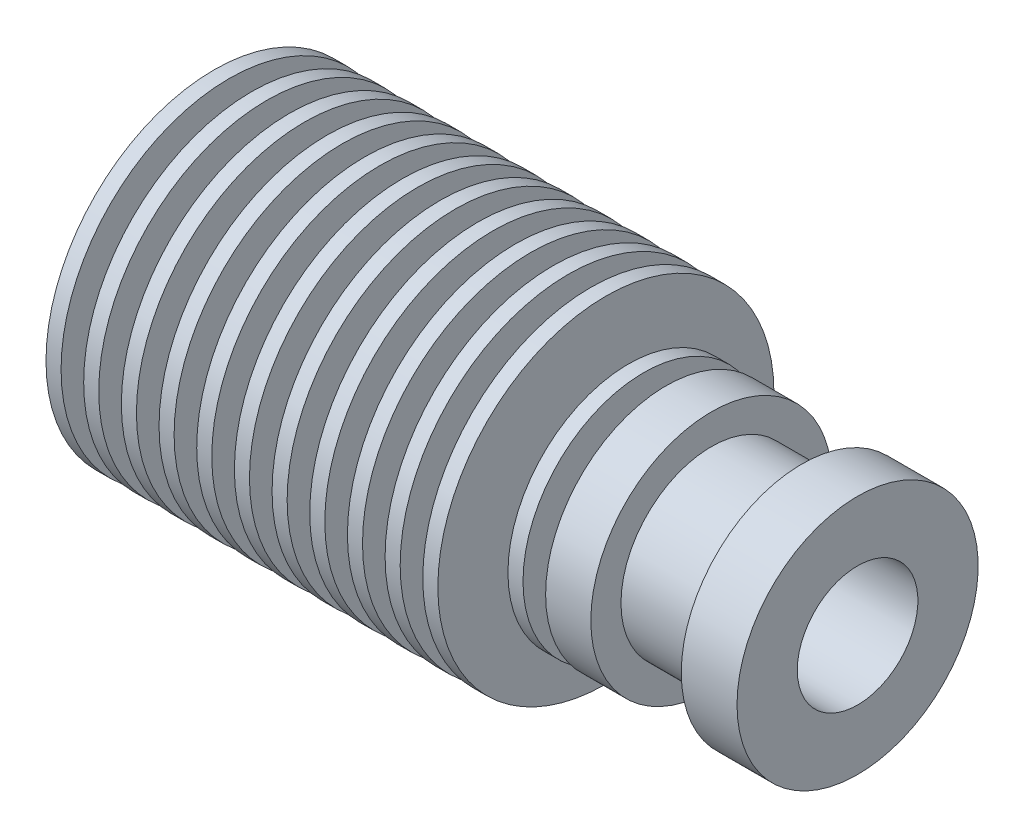
SolidWorks part; units mm, degrees
material "1060 Alloy"
ref_plane "Front Plane" through (0, 0, 0) normal (0, 0, 1) x (1, 0, 0)
ref_plane "Top Plane" through (0, 0, 0) normal (0, 1, 0) x (1, 0, 0)
ref_plane "Right Plane" through (0, 0, 0) normal (1, 0, 0) x (0, 0, -1)
sketch "Sketch1" plane through (0, 0, 0) normal (0, 0, 1) x (1, 0, 0)
  line L5 (9.7, 11.5342) -> (6, 11.5342)
  line L6 (6, 11.5342) -> (6, 13.5342)
  line L7 (6, 13.5342) -> (0, 13.5342)
  line L8 (0, 13.5342) -> (0, 11.5342)
  line L9 (0, 11.5342) -> (-3, 11.5342)
  line L10 (-3, 11.5342) -> (-3, 15.5342)
  line L12 (-32, 14.0576) -> (-30.5, 14.134)
  line L13 (-33, 14.0142) -> (-33, 8.3842)
  line L14 (-33, 8.3842) -> (-32, 8.3842)
  line L15 (-32, 8.3842) -> (-32, 14.0576)
  line L16 (-29.5, 8.3842) -> (-29.5, 14.1849)
  line L17 (-30.5, 14.134) -> (-30.5, 8.3842)
  line L18 (-30.5, 8.3842) -> (-29.5, 8.3842)
  line L19 (-27, 8.3842) -> (-27, 14.3122)
  line L20 (-28, 14.2613) -> (-28, 8.3842)
  line L21 (-28, 8.3842) -> (-27, 8.3842)
  line L22 (-24.5, 8.3842) -> (-24.5, 14.4395)
  line L23 (-25.5, 14.3886) -> (-25.5, 8.3842)
  line L24 (-25.5, 8.3842) -> (-24.5, 8.3842)
  line L25 (-22, 8.3842) -> (-22, 14.5668)
  line L26 (-23, 14.5159) -> (-23, 8.3842)
  line L27 (-23, 8.3842) -> (-22, 8.3842)
  line L28 (-19.5, 8.3842) -> (-19.5, 14.6941)
  line L29 (-20.5, 14.6432) -> (-20.5, 8.3842)
  line L30 (-20.5, 8.3842) -> (-19.5, 8.3842)
  line L31 (-17, 8.3842) -> (-17, 14.8214)
  line L32 (-18, 14.7705) -> (-18, 8.3842)
  line L33 (-18, 8.3842) -> (-17, 8.3842)
  line L34 (-14.5, 8.3842) -> (-14.5, 14.9487)
  line L35 (-15.5, 14.8977) -> (-15.5, 8.3842)
  line L36 (-15.5, 8.3842) -> (-14.5, 8.3842)
  line L37 (-12, 8.3842) -> (-12, 15.076)
  line L38 (-13, 15.025) -> (-13, 8.3842)
  line L39 (-13, 8.3842) -> (-12, 8.3842)
  line L40 (-9.5, 8.3842) -> (-9.5, 15.2032)
  line L41 (-10.5, 15.1523) -> (-10.5, 8.3842)
  line L42 (-10.5, 8.3842) -> (-9.5, 8.3842)
  line L43 (-7, 8.3842) -> (-7, 15.3305)
  line L44 (-8, 15.2796) -> (-8, 8.3842)
  line L45 (-8, 8.3842) -> (-7, 8.3842)
  line L46 (-7, 15.3305) -> (-5.5, 15.4069)
  line L47 (-9.5, 15.2032) -> (-8, 15.2796)
  line L48 (-12, 15.076) -> (-10.5, 15.1523)
  line L49 (-14.5, 14.9487) -> (-13, 15.025)
  line L50 (-17, 14.8214) -> (-15.5, 14.8977)
  line L51 (-19.5, 14.6941) -> (-18, 14.7705)
  line L52 (-22, 14.5668) -> (-20.5, 14.6432)
  line L53 (-24.5, 14.4395) -> (-23, 14.5159)
  line L54 (-27, 14.3122) -> (-25.5, 14.3886)
  line L55 (-29.5, 14.1849) -> (-28, 14.2613)
  line L56 (-4.5, 11.5342) -> (-4.5, 15.4578)
  line L57 (-5.5, 15.4069) -> (-5.5, 11.5342)
  line L58 (-5.5, 11.5342) -> (-4.5, 11.5342)
  line L59 (-4.5, 15.4578) -> (-3, 15.5342)
  line L60 (9.7, 15.5342) -> (3.2, 15.5342)
  line L61 (9.7, 15.5342) -> (9.7, 11.5342)
  line L62 (-33, 19.5342) -> (9.7, 19.5342) construction
  line L63 (3.2, 15.5342) -> (1.3, 17.4342)
  line L65 (-33, 16.5342) -> (-17.9, 16.5342)
  line L67 (-33, 16.5342) -> (-33, 14.0142)
  line L68 (-17.9, 16.5342) -> (-17, 17.4342)
  line L70 (1.3, 17.4342) -> (-17, 17.4342)
  dimension "D2" = 3.7
  dimension "D3" = 6
  dimension "D4" = 6.5
  dimension "D5" = 135
  dimension "D6" = 3
  dimension "D7" = 4
  dimension "D8" = 8
  dimension "D9" = 5.52
  dimension "D10" = 11.15
  dimension "D11" = 1
  dimension "D14" = 16
  dimension "D13" = 12
  dimension "D15" = 16
  dimension "D16" = 135
  dimension "D17" = 42.7
  dimension "D18" = 15.1
  dimension "D19" = 3
  dimension "D20" = 4.2
  dimension "D12" = 11
revolve "Revolve1" add sketch "Sketch1" angle 360 about L62
thread "Thread1" pitch 1 start angle 0, offset 0, length 0, pitch 1, diameter 6
ref_plane "Plane2" through (-17.9, 19.5342, 3) normal (0, -1, 0) x (0, 0, 1)
sketch "Thread Profile2" plane through (-17.9, 19.5342, 3) normal (0, -1, 0) x (0, 0, 1)
  line L0 (0, 0) -> (0, 1) construction
  line L1 (0, 0) -> (0.5413, 0.3125)
  line L2 (0.5413, 0.3125) -> (0.5413, 0.4375)
  line L3 (0.5413, 0.4375) -> (0, 0.75)
  line L4 (0.5413, 0.375) -> (0, 0.375) construction
  line L11 (0, 0) -> (0, 0.75)
  point P2 (0, 0)
  dimension "Pitch" = 1
  dimension "Profile_Angle" = 60
  dimension "Profile_Land" = 0.125
  dimension "Profile_Height" = 0.5413
